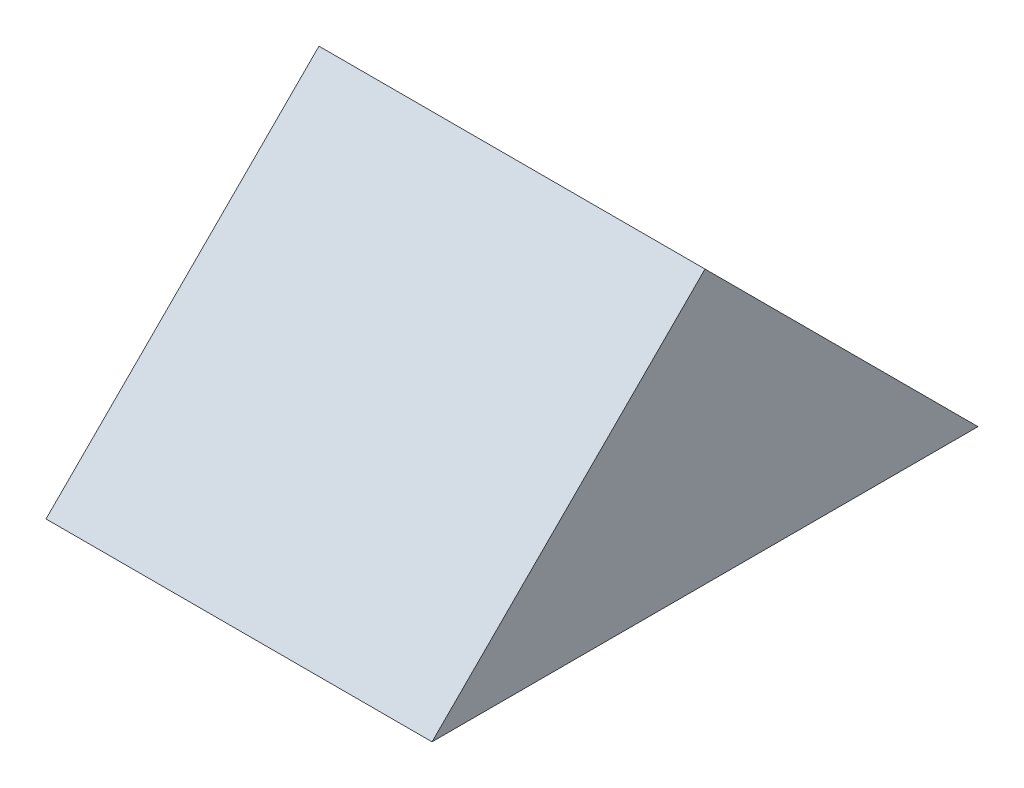
SolidWorks part; units mm, degrees
ref_plane "Спереди" through (0, 0, 0) normal (0, 0, 1) x (1, 0, 0)
ref_plane "Сверху" through (0, 0, 0) normal (0, 1, 0) x (1, 0, 0)
ref_plane "Справа" through (0, 0, 0) normal (1, 0, 0) x (0, 0, -1)
sketch "Эскиз1" plane through (0, 0, 0) normal (1, 0, 0) x (0, 0, -1)
  line L0 (0, 21.2132) -> (-21.2132, 0)
  line L1 (-21.2132, 0) -> (21.2132, 0)
  line L2 (21.2132, 0) -> (0, 21.2132)
  point P2 (0, 0)
  dimension "D1" = 30
extrude "Бобышка-Вытянуть3" add sketch "Эскиз1" along normal blind 15 and the other way blind 15
sketch "Эскиз4" plane through (0, 10.6066, 10.6066) normal (0, 0.7071, 0.7071) x (1, 0, 0)
  line L0 (0, 10) -> (0, -10) construction
  line L1 (-10, 0) -> (10, 0) construction
  circle A0 centre (0, 0) radius 10 construction
  dimension "D1" = 20
sketch "Эскиз5" plane through (0, 6.2132, -15) normal (0, -0.7071, 0.7071) x (1, 0, 0)
  line L0 (0, 16.2132) -> (0, -3.7868) construction
  line L1 (-10, 6.2132) -> (10, 6.2132) construction
  circle A0 centre (0, 6.2132) radius 10 construction
  dimension "D1" = 20
